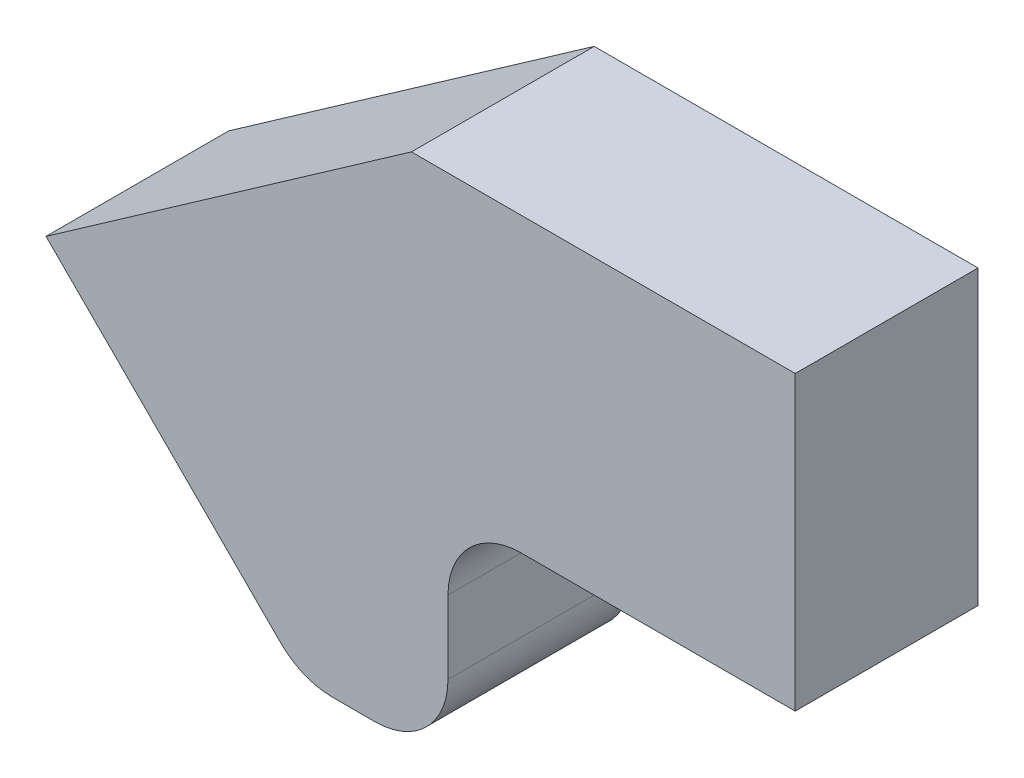
SolidWorks part; units mm, degrees
material "PBT General Purpose"
ref_plane "Front Plane" through (0, 0, 0) normal (0, 0, 1) x (1, 0, 0)
ref_plane "Top Plane" through (0, 0, 0) normal (0, 1, 0) x (1, 0, 0)
ref_plane "Right Plane" through (0, 0, 0) normal (1, 0, 0) x (0, 0, -1)
sketch "frame_outline" plane through (0, 0, 0) normal (0, 0, 1) x (1, 0, 0)
  line L80 (0, 0) -> (0.4999, 0.35)
  line L83 (0.4999, 0.35) -> (1.0249, 0.35)
  line L84 (1.0249, 0.35) -> (1.0249, -0.05)
  line L85 (1.0249, -0.05) -> (0.5499, -0.05)
  line L86 (0.5499, -0.05) -> (0.5499, -0.35)
  line L87 (0.5499, -0.35) -> (0.35, -0.35)
  line L88 (0.35, -0.35) -> (0, 0)
  line L89 (0, 0) -> (0.55, 0) construction
  dimension "D18" = 0.4
  dimension "D20" = 0.3
  dimension "D23" = 35
  dimension "D21" = 0.525
  dimension "D22" = 45
  dimension "D3" = 0.475
  dimension "D4" = 0.05
  dimension "D5" = 0.6102
extrude "Boss-Extrude1" add sketch "frame_outline" along normal mid plane 0.25
fillet "Fillet1" radius 0.1 3 edges at (0.5499, -0.35, 0) (0.5499, -0.05, 0) (0.35, -0.35, 0)
equation "\"t\"= 0.25'thickness of the sheets"
equation "\"t_cf\"= 0.115'thickness of single carbon fiber layer"
equation "\"t_kapton\"= 0.025'thickness of single Kapton flex layer"
equation "\"t_fr4\"= 0.1'thickness of FR4 with copper layer"
equation "\"joint_flex\"= 0.1'Width of flextures gap"
equation "\"joint_flex_eff\"= 0.02'Width of flecture after castelation"
equation "\"joint_fold\"= 0.2'Width of folding joints for 90deg fold"
equation "\"gap_tolerance\"= 0.002'Width to have interfecence fit between carbon fiber inserts"
equation "\"assemble_angle\"= 90'Angle of assembly parts"
equation "\"D1@Boss-Extrude1\"=\"t\""
equation "\"link_lift\"= 0.5'Actuation linkage amplification for the lift motion"
equation "\"link_swing\"= 0.45'Actuation linkage amplification for the swing motion"
equation "\"D21@frame_outline\"=1.05 + \"joint_flex\"/2 -\"link_swing\"-\"t\"/2"
equation "\"D3@frame_outline\"=\"t\"*2.5-\"joint_fold\"+0.05"
